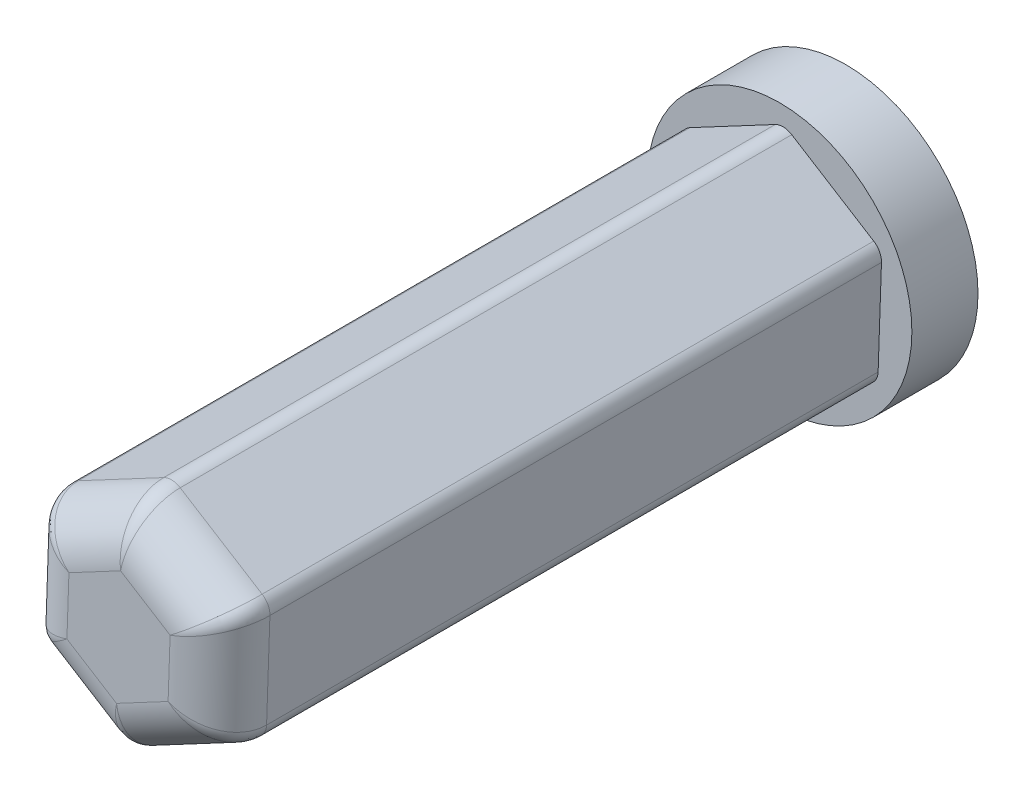
SolidWorks part; units mm, degrees
ref_plane "Front Plane" through (0, 0, 0) normal (0, 0, 1) x (1, 0, 0)
ref_plane "Top Plane" through (0, 0, 0) normal (0, 1, 0) x (1, 0, 0)
ref_plane "Right Plane" through (0, 0, 0) normal (1, 0, 0) x (0, 0, -1)
sketch "Sketch1" plane through (0, 0, 0) normal (0, 0, 1) x (1, 0, 0)
  line L7 (-0.0748, -0.0574) -> (-3.0436, 1.7963)
  line L8 (-3.0436, 1.7963) -> (-6.1333, 0.1521)
  line L9 (-6.1333, 0.1521) -> (-6.2543, -3.3458)
  line L10 (-6.2543, -3.3458) -> (-3.2855, -5.1995)
  line L11 (-3.2855, -5.1995) -> (-0.1958, -3.5553)
  line L12 (-0.1958, -3.5553) -> (-0.0748, -0.0574)
  circle A0 centre (-3.1645, -1.7016) radius 3.0311 construction
  dimension "D1" = 3.5
extrude "Boss-Extrude1" add sketch "Sketch1" along normal blind 20
fillet "Fillet1" radius 0.5 6 edges at (-6.2543, -3.3458, 10) (-3.2855, -5.1995, 10) (-6.1333, 0.1521, 10) (-0.1958, -3.5553, 10) (-0.0748, -0.0574, 10) (-3.0436, 1.7963, 10)
fillet "Fillet2" radius 1.5 12 edges at (-6.0677, 0.1112, 20) (-4.5884, 0.9742, 20) (-3.0462, 1.719, 20) (-1.5592, 0.8695, 20) (-0.1431, -0.0938, 20) (-0.1353, -1.8064, 20) (-0.2614, -3.5144, 20) (-1.7406, -4.3774, 20) (-3.2829, -5.1222, 20) (-4.7699, -4.2726, 20) (-6.186, -3.3094, 20) (-6.1938, -1.5968, 20)
sketch "Sketch2" plane through (0, 0, 0) normal (0, 0, -1) x (-1, 0, 0)
  line L0 (3.0462, 1.719) -> (3.2829, -5.1222)
  arc A0 (3.2984, 1.6607) -> (2.7987, 1.6434) centre (3.0635, 1.2193) ccw construction
  arc A1 (3.0307, -5.0639) -> (3.5304, -5.0466) centre (3.2656, -4.6225) ccw construction
  circle A2 centre (3.1645, -1.7016) radius 4
  line M1 (3.5304, -5.0466) -> (6.0095, -3.4987)
  arc M2 (6.0095, -3.4987) -> (6.2443, -3.0573) centre (5.7446, -3.0745) ccw
  line M3 (6.2443, -3.0573) -> (6.1433, -0.1364)
  arc M4 (6.1433, -0.1364) -> (5.8785, 0.2878) centre (5.6436, -0.1536) ccw
  line M5 (5.8785, 0.2878) -> (3.2984, 1.6607)
  arc M6 (3.2984, 1.6607) -> (2.7987, 1.6434) centre (3.0635, 1.2193) ccw
  line M7 (2.7987, 1.6434) -> (0.3196, 0.0955)
  arc M8 (0.3196, 0.0955) -> (0.0848, -0.3459) centre (0.5845, -0.3286) ccw
  line M9 (0.0848, -0.3459) -> (0.1858, -3.2668)
  arc M10 (0.1858, -3.2668) -> (0.4506, -3.6909) centre (0.6855, -3.2495) ccw
  line M11 (0.4506, -3.6909) -> (3.0307, -5.0639)
  arc M12 (3.0307, -5.0639) -> (3.5304, -5.0466) centre (3.2656, -4.6225) ccw
extrude "Boss-Extrude2" add sketch "Sketch2" along normal blind 2 contours A2 M1 M12 M11 M10 M9 M8 M7 M6 M5 M4 M3 M2 | L0 M6 M12 M1 M2 M3 M4 M5 | L0 M6 M7 M8 M9 M10 M11 M12 region at (-4.5092, -1.6551, 0) region at (-1.8199, -1.7481, 0) region at (0.7223, -1.7016, 0)
